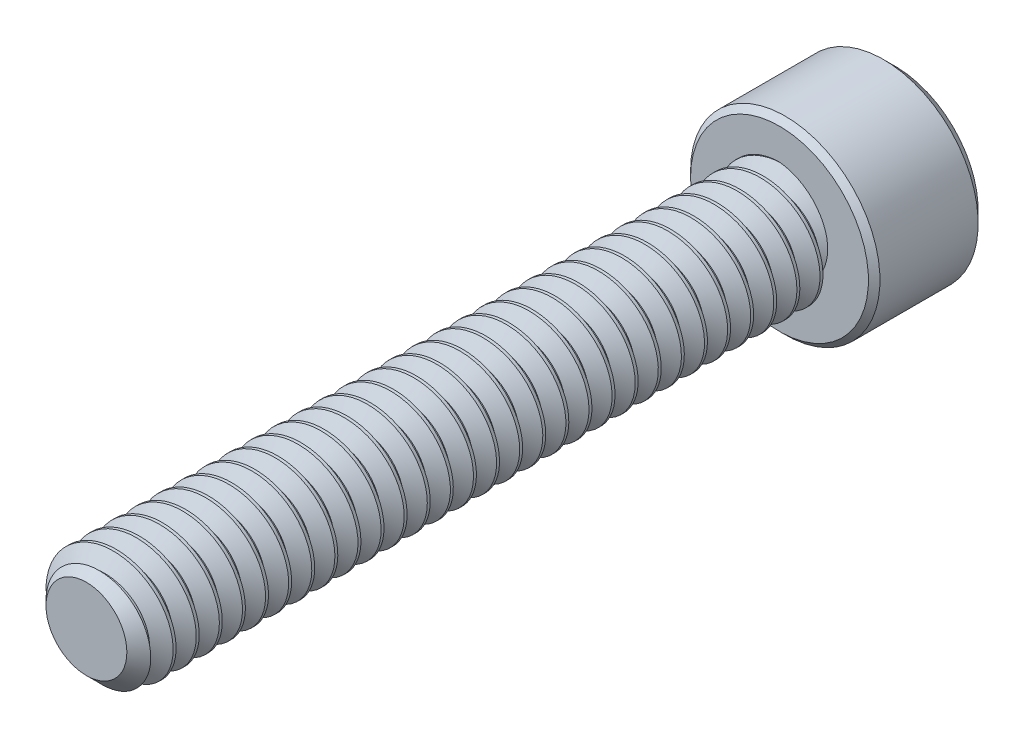
SolidWorks part; units mm, degrees
ref_plane "Front Plane" through (0, 0, 0) normal (0, 0, 1) x (1, 0, 0)
ref_plane "Top Plane" through (0, 0, 0) normal (0, 1, 0) x (1, 0, 0)
ref_plane "Right Plane" through (0, 0, 0) normal (1, 0, 0) x (0, 0, -1)
sketch "Sketch1" plane through (0, 0, 0) normal (0, 0, 1) x (1, 0, 0)
  line L0 (0, 1.5875) -> (0, -1.5875) construction
  circle A0 centre (0, 0) radius 1.5875
  dimension "OD" = 3.175
extrude "Extrude1" add sketch "Sketch1" against normal blind 19.05
sketch "Sketch2" plane through (0, 0, 0) normal (0, 0, 1) x (1, 0, 0)
  circle A0 centre (0, 0) radius 1.5875 construction
  circle A1 centre (0, 0) radius 1.5875
curve "Helix/Spiral1" pitch 0.635 height 19.685 turns 31 parameters "pitch"=0.635
chamfer "Chamfer3" distance 0.4763 angle 45 1 edges at (1.5875, 0, 0)
sketch "Sketch3" plane through (0, 0, 0) normal (1, 0, 0) x (0, 0, -1)
  line L0 (-0.5556, 1.5875) -> (-0.3175, 1.1751)
  line L1 (-0.3175, 1.1751) -> (-0.2381, 1.1751)
  line L2 (-0.2381, 1.1751) -> (0, 1.5875)
  line L3 (-0.5556, 1.5875) -> (0, 1.5875)
  line L4 (-0.2778, 1.5875) -> (-0.2778, 1.1751) construction
  line L5 (-0.4366, 1.3813) -> (-0.1191, 1.3813) construction
  line L6 (0, 1.5875) -> (0, -1.5875) construction
  dimension "D1" = 0.0794
  dimension "D2" = 0.3175
  dimension "D3" = 60
sweep "Cut-Sweep1" cut profiles "Sketch3" path "Helix/Spiral1"
sketch "Sketch6" plane through (0, 0, -19.05) normal (0, 0, -1) x (-1, 0, 0)
  circle A0 centre (0, 0) radius 2.6035
  dimension "head dia" = 5.207
extrude "Extrude2" add sketch "Sketch6" along normal blind 3.175
sketch "Sketch7" plane through (0, 0, -22.225) normal (0, 0, -1) x (-1, 0, 0)
  line L1 (0, 1.3748) -> (-1.1906, 0.6874)
  line L2 (-1.1906, 0.6874) -> (-1.1906, -0.6874)
  line L3 (-1.1906, -0.6874) -> (0, -1.3748)
  line L4 (0, -1.3748) -> (1.1906, -0.6874)
  line L5 (1.1906, -0.6874) -> (1.1906, 0.6874)
  line L6 (1.1906, 0.6874) -> (0, 1.3748)
  circle A0 centre (0, 0) radius 1.1906 construction
  dimension "hex dia" = 2.3813
extrude "Cut-Extrude1" cut sketch "Sketch7" against normal blind 1.7859
sketch "Sketch8" plane through (0, 0, -22.225) normal (0, 0, -1) x (-1, 0, 0)
  circle A0 centre (0, 0) radius 1.3748
extrude "Cut-Extrude2" cut sketch "Sketch8" against normal blind 0.3175 draft 45
chamfer "Chamfer1" distance 0.3175 angle 45 1 edges at (-2.6035, 0, -22.225)
chamfer "Chamfer2" distance 0.1588 angle 45 1 edges at (-2.6035, 0, -19.05)
sketch "Sketch9" plane through (0, 0, 0) normal (1, 0, 0) x (0, 0, -1)
  line L0 (0, 1.5875) -> (0, -1.5875) construction
  line L1 (3.4925, 1.5875) -> (3.4925, -1.5875) construction
  line L2 (19.05, 2.6035) -> (19.05, -2.6035) construction
  line L3 (22.225, 2.6035) -> (22.225, -2.6035) construction
  line L4 (22.225, 0) -> (0, 0) construction
  dimension "D1" = 3.4925
  dimension "D2" = 3.175
  dimension "D3" = 5.207
  dimension "D4" = 19.05
equation "\"D3@Helix/Spiral1\" = \"screw length@Extrude1\"+\"pitch@Helix/Spiral1\""
equation "\"D1@Sketch3\" = \"pitch@Helix/Spiral1\"*.125"
equation "\"D2@Sketch3\" = \"pitch@Helix/Spiral1\"*.5"
equation "\"D1@Cut-Extrude1\" = \"hex dia@Sketch7\"*.75"
equation "\"D1@Chamfer1\" = \"head depth@Extrude2\"/10"
equation "\"D1@Sketch9\" = \"pitch@Helix/Spiral1\"*5.5"
equation "\"D1@Chamfer2\" = \"D1@Chamfer1\"/2"
equation "\"D1@Cut-Extrude2\" = \"D1@Chamfer2\"*2"
equation "\"D1@Chamfer3\" = \"pitch@Helix/Spiral1\"*.750"
equation "\"D2@Sketch9\" = \"head depth@Extrude2\""
equation "\"D3@Sketch9\" = \"head dia@Sketch6\""
equation "\"D4@Sketch9\" = \"screw length@Extrude1\""
